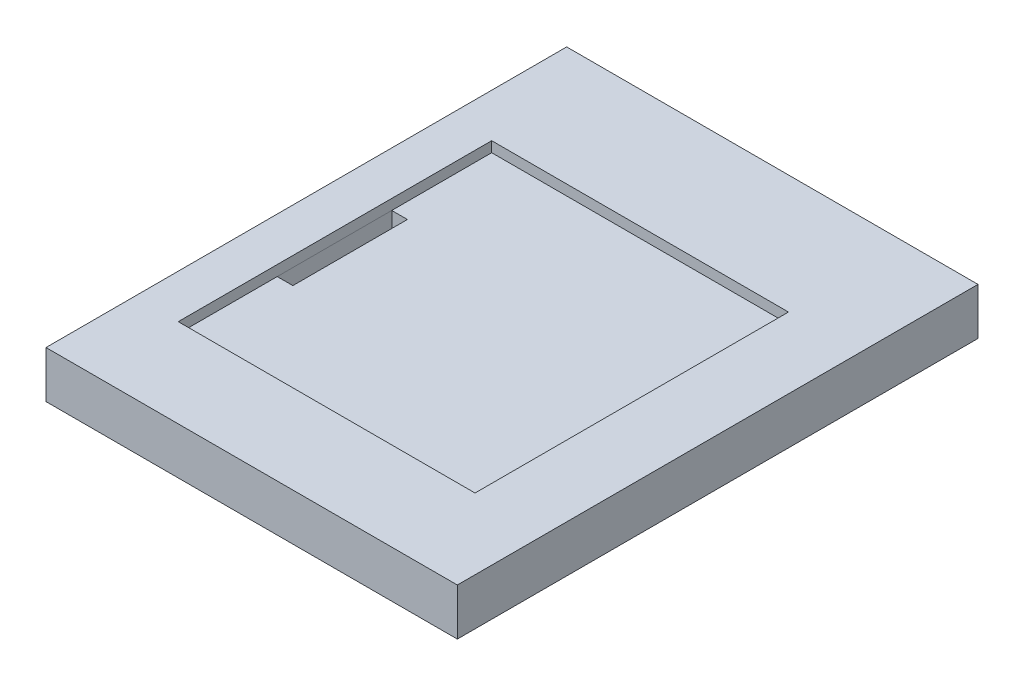
SolidWorks part; units mm, degrees
ref_plane "Front Plane" through (0, 0, 0) normal (0, 0, 1) x (1, 0, 0)
ref_plane "Top Plane" through (0, 0, 0) normal (0, 1, 0) x (1, 0, 0)
ref_plane "Right Plane" through (0, 0, 0) normal (1, 0, 0) x (0, 0, -1)
sketch "Sketch3" plane through (0, 0, 0) normal (0, 1, 0) x (1, 0, 0)
  line L1 (0, 0) -> (39.5, 0)
  line L2 (0, 0) -> (0, 50)
  line L3 (0, 50) -> (39.5, 50)
  line L4 (39.5, 0) -> (39.5, 50)
  line L5 (3, 3) -> (36.5, 3)
  line L6 (3, 3) -> (3, 47)
  line L7 (3, 47) -> (36.5, 47)
  line L8 (36.5, 3) -> (36.5, 47)
  dimension "D1" = 50
  dimension "D2" = 39.5
  dimension "D3" = 3
  dimension "D4" = 3
  dimension "D5" = 33.5
  dimension "D6" = 44
extrude "Boss-Extrude1" add sketch "Sketch3" along normal blind 2
sketch "Sketch4" plane through (0, 2, 0) normal (0, 1, 0) x (1, 0, 0)
  line L1 (0, 0) -> (39.5, 0)
  line L2 (0, 0) -> (0, 50)
  line L3 (0, 50) -> (39.5, 50)
  line L4 (39.5, 0) -> (39.5, 50)
extrude "Boss-Extrude2" add sketch "Sketch4" along normal blind 1.5
sketch "Sketch5" plane through (0, 3.5, 0) normal (0, 1, 0) x (1, 0, 0)
  line L0 (0, 50) -> (0, 0) construction
  line L1 (4.206, 29) -> (5.706, 29)
  line L2 (4.206, 29) -> (4.206, 18)
  line L3 (4.206, 18) -> (5.706, 18)
  line L4 (5.706, 29) -> (5.706, 18)
  line L5 (0, 0) -> (39.5, 0) construction
  dimension "D1" = 4.206
  dimension "D2" = 18
  dimension "D3" = 11
  dimension "D4" = 1.5
extrude "Cut-Extrude1" cut sketch "Sketch5" against normal blind 3
sketch "Sketch6" plane through (0, 0, 0) normal (0, -1, 0) x (1, 0, 0)
  line L0 (39.5, -50) -> (0, -50) construction
  line L1 (0, -50) -> (0, 0) construction
  line L2 (39.5, 0) -> (39.5, -50) construction
  circle A0 centre (1.5, -47.5) radius 0.75
  circle A1 centre (38, -47.5) radius 0.75
  dimension "D1" = 1.5
  dimension "D4" = 1.5
  dimension "D2" = 2.5
  dimension "D3" = 1.5
  dimension "D5" = 2.5
  dimension "D6" = 1.5
extrude "Cut-Extrude2" cut sketch "Sketch6" against normal blind 2.5
pattern_linear "LPattern1" count 4 spacing 15 along (0, 0, 1) of "Cut-Extrude2"
sketch "Sketch7" plane through (0, 3.5, 0) normal (0, 1, 0) x (1, 0, 0)
  line L0 (39.5, 0) -> (39.5, 50) construction
  line L1 (0, 50) -> (39.5, 50)
  line L2 (0, 50) -> (0, 0)
  line L3 (0, 0) -> (39.5, 0)
  line L4 (39.5, 50) -> (39.5, 0)
  line L6 (4.2, 38.6) -> (32.7, 38.6)
  line L7 (4.2, 38.6) -> (4.2, 8.5)
  line L8 (4.2, 8.5) -> (32.7, 8.5)
  line L9 (32.7, 38.6) -> (32.7, 8.5)
  dimension "D1" = 28.5
  dimension "D2" = 30.1
  dimension "D3" = 11.4
  dimension "D4" = 4.2
extrude "Boss-Extrude3" add sketch "Sketch7" along normal blind 1
